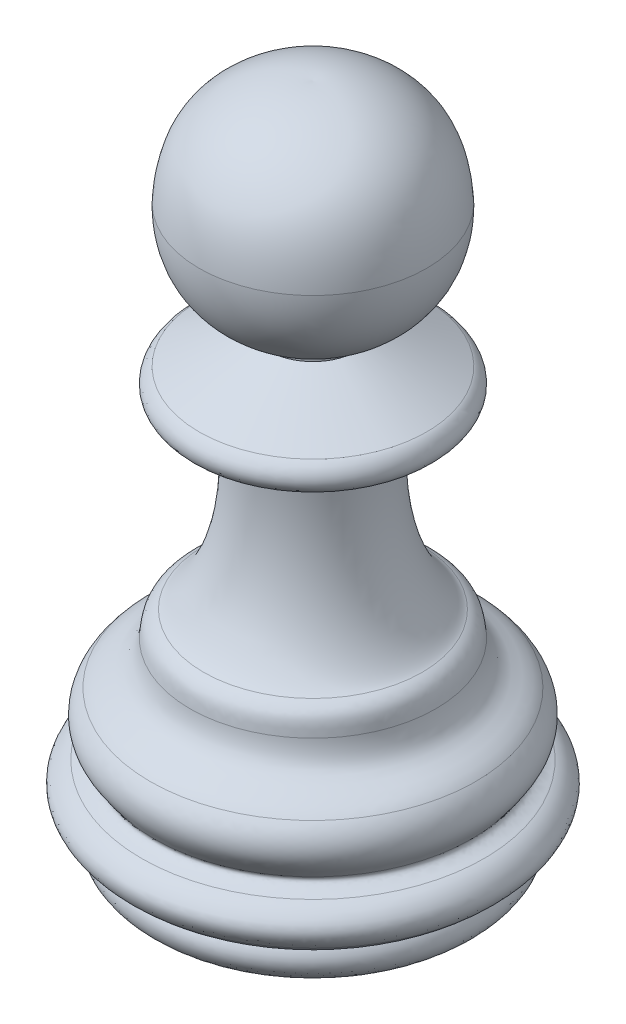
SolidWorks part; units mm, degrees
ref_plane "Front Plane" through (0, 0, 0) normal (0, 0, 1) x (1, 0, 0)
ref_plane "Top Plane" through (0, 0, 0) normal (0, 1, 0) x (1, 0, 0)
ref_plane "Right Plane" through (0, 0, 0) normal (1, 0, 0) x (0, 0, -1)
sketch "Sketch1" plane through (0, 0, 0) normal (0, 0, 1) x (1, 0, 0)
  line L0 (0, 26.6251) -> (0, 0)
  line L1 (-6.2477, 3.8979) -> (0, 3.8979) construction
  line L2 (0, 3.8979) -> (6.2477, 3.8979) construction
  line L3 (1.749, 18.5191) -> (1.749, 18.2829)
  line L4 (1.749, 18.2829) -> (4.479, 16.8884)
  line L5 (4.1468, 15.6897) -> (2.7359, 15.6897)
  line L6 (0, 0) -> (5.5438, 0)
  spline S0 degree 3 poles (0, 26.6251) (1.262, 26.7204) (3.7808, 25.7024) (4.4106, 23.5673) (4.479, 22.4656) knots 0 0 0 0 0.578604 1 1 1 1
  spline S1 degree 2 poles (4.479, 22.4656) (4.4933, 19.7247) (1.749, 18.5191) knots 0 0 0 1 1 1
  spline S2 degree 3 poles (4.479, 16.8884) (4.6795, 16.786) (5.0672, 16.164) (4.4935, 15.6897) (4.1468, 15.6897) knots 0 0 0 0 0.447467 1 1 1 1
  spline S3 degree 3 poles (2.7359, 15.6897) (2.1364, 11.1363) (3.7161, 8.9024) (4.3019, 8.6049) knots 0 0 0 0 1 1 1 1
  spline S4 degree 3 poles (4.3019, 8.6049) (4.4597, 8.5248) (4.7787, 8.2759) (4.7999, 7.8941) (4.834, 7.6252) knots 0 0 0 0 0.408406 1 1 1 1
  spline S5 degree 3 poles (4.834, 7.6252) (4.8747, 7.3037) (5.109, 6.4492) (6.007, 6.3433) (6.4024, 5.9302) knots 0 0 0 0 0.377645 1 1 1 1
  spline S6 degree 3 poles (6.4024, 5.9302) (6.7842, 5.5313) (6.9517, 4.7282) (6.4263, 4.16) (6.2477, 3.8979) knots 0 0 0 0 0.588502 1 1 1 1
  spline S7 degree 3 poles (6.2477, 3.8979) (6.2187, 3.8553) (6.1839, 3.7178) (6.4451, 3.5733) (6.69, 3.498) (6.7414, 3.4785) knots 0 0 0 0 0.162367 0.584346 1 1 1 1
  spline S8 degree 3 poles (6.7414, 3.4785) (6.9707, 3.391) (7.4012, 3.0391) (7.5394, 2.5201) (7.0853, 2.0556) knots 0 0 0 0 0.372722 1 1 1 1
  spline S9 degree 3 poles (7.0853, 2.0556) (6.8647, 1.83) (6.6096, 1.6534) (6.3198, 1.5258) knots 0 0 0 0 1 1 1 1
  spline S10 degree 2 poles (6.3198, 1.5258) (6.8893, 0.6863) (5.5438, 0) knots 0 0 0 1 1 1
  point P31 (0, 26.7986)
  dimension "D1" = 6.2477
  dimension "D2" = 6.2477
revolve "Revolve2" add sketch "Sketch1" angle 360 about L0
